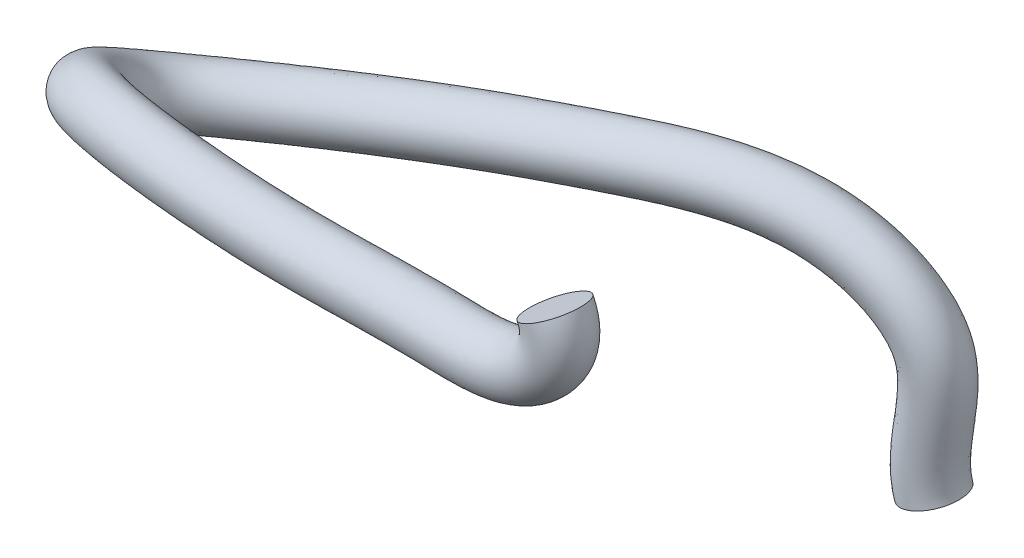
SolidWorks part; units mm, degrees
ref_plane "前视基准面" through (0, 0, 0) normal (0, 0, 1) x (1, 0, 0)
ref_plane "上视基准面" through (0, 0, 0) normal (0, 1, 0) x (1, 0, 0)
ref_plane "右视基准面" through (0, 0, 0) normal (1, 0, 0) x (0, 0, -1)
other "Configuration Table"
sketch3d "3D草图1"
  spline S0 degree 3 poles (0, 0.35, 0) (-0.848, 3.296, 0.137) (2.2141, 9.8705, -0.3576) (-7.303, 17.43, 1.1795) (-19.7284, 17.201, 6.4216) (-32.4243, 15.6492, 11.075) (-44.2113, 16.2906, 20.5581) (-38.4038, 24.6145, 31.0952) (-23.3774, 21.0354, 29.6248) (-11.949, 22.3096, 30.0451) (-1.9737, 21.6747, 29.9917) (1.0724, 25.8858, 30.0025) (0, 28, 30) knots 0 0 0 0 0.086606 0.150699 0.28532 0.43415 0.543701 0.613796 0.749609 0.88423 0.947691 1 1 1 1
sweep "扫描1" add path "3D草图1" circular profile diameter 4.5 parameters "D3"=4.5
